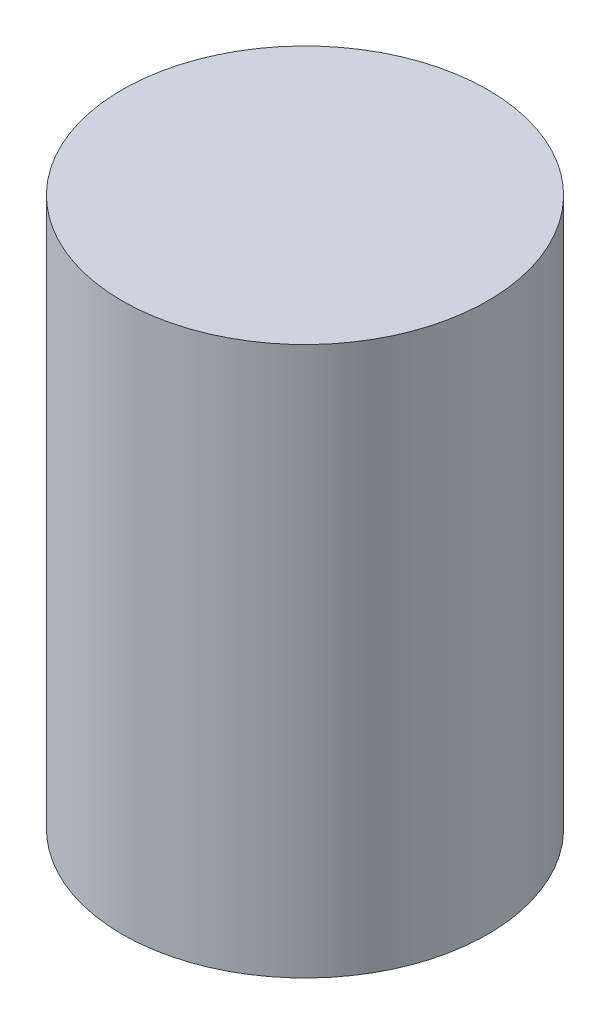
SolidWorks part; units mm, degrees
ref_plane "Front Plane" through (0, 0, 0) normal (0, 0, 1) x (1, 0, 0)
ref_plane "Top Plane" through (0, 0, 0) normal (0, 1, 0) x (1, 0, 0)
ref_plane "Right Plane" through (0, 0, 0) normal (1, 0, 0) x (0, 0, -1)
sketch "Sketch1" plane through (0, 0, 0) normal (0, 1, 0) x (1, 0, 0)
  circle A0 centre (0, 0) radius 1
  dimension "D1" = 2
extrude "Boss-Extrude1" add sketch "Sketch1" along normal blind 3
